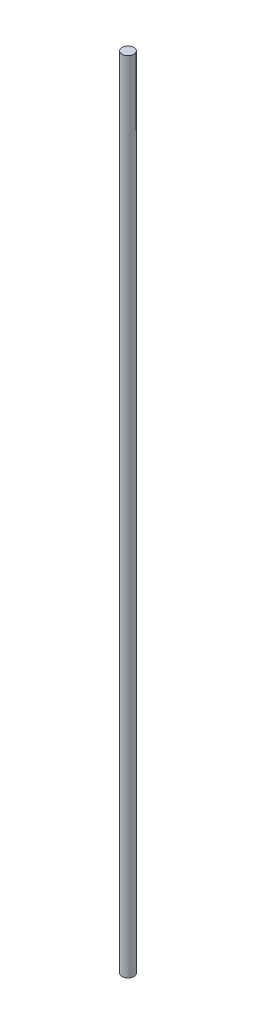
SolidWorks part; units mm, degrees
ref_plane "Спереди" through (0, 0, 0) normal (0, 0, 1) x (1, 0, 0)
ref_plane "Сверху" through (0, 0, 0) normal (0, 1, 0) x (1, 0, 0)
ref_plane "Справа" through (0, 0, 0) normal (1, 0, 0) x (0, 0, -1)
sketch "Эскиз2" plane through (0, 0, 0) normal (0, 0, 1) x (1, 0, 0)
  line L5 (-2.5, 167.95) -> (0, 167.95)
  line L6 (-2.5, 167.95) -> (-2.5, -167.95)
  line L7 (-2.5, -167.95) -> (0, -167.95)
  line L8 (0, 167.95) -> (0, -167.95)
  line L9 (-2.5, 167.95) -> (0, -167.95) construction
  line L10 (-2.5, -167.95) -> (0, 167.95) construction
  point P0 (-1.25, 0)
  point P5 (0, 0)
  dimension "D1" = 2.5
  dimension "D2" = 335.9
revolve "Повернуть1" add sketch "Эскиз2" angle 360 about L6
equation "\"Ширина груза\"= 160"
equation "\"Глубина груза\"= 240"
equation "\"Высота груза\"= 160"
equation "\"Ширина ячейки\"= \"Ширина груза\" + 10"
equation "\"Глубина ячейки\"= \"Глубина груза\" + 10"
equation "\"Высота ячейки\"= \"Высота груза\" + 10 + 13"
equation "\"Колво ячеек ширина\"= 2"
equation "\"Колво ячеек высота\"= 2"
equation "\"Толщина стенки\" = \"Толщина тонких панелей\""
equation "\"Крепление дверцы\"= 5 "
equation "\"Ширина рейки\"= \"Толщина шестерни\""
equation "\"Высота рейки\"= 20"
equation "\"Высота пола\" = 2*\"Толщина тонких панелей\""
equation "\"Колво полозьев\"= 5"
equation "\"Отступ рейки\"= 20"
equation "\"Глубина каретки\"= \"Глубина ячейки\" + 30 + \"Мотор Y высота корпуса\" + 20 + \"Удлинение платформы по глубине\""
equation "\"Длинна рейки\" = (\"Ширина ячейки\"+\"Толщина вертикальных стенок\"+\"Крепление дверцы\")*\"Колво ячеек ширина\"+\"Ширина ячейки выгрузки\"*\"Колво выгрузки\"+\"Толщина вертикальных стенок\"+2*\"Отступ крепления мотора фиксации\"-\"Крепление дверцы\"*\"Колво ячеек ширина\""
equation "\"Отступ шпильки\"= 26"
equation "\"Диаметр шпильки\"= 5"
equation "\"Длинна шпильки\" = (\"Высота ячейки\"+\"Толщина горизонтальных плит\"+\"Высота пола\")*\"Колво ячеек высота\"+2*(\"Толщина горизонтальных плит\"+\"Отступ рейки\")"
equation "\"D1@Эскиз2\"= \"Диаметр шпильки\" / 2"
equation "\"D2@Эскиз2\" = \"Глубина каретки\" - \"Мотор Y высота корпуса\" - \"Толщина стенки\""
equation "\"Ширина пластины\" = 50"
equation "\"Высота зона выгрузки\"= \"Высота ячейки\" * 2 + \"Толщина стенки\" * 2"
equation "\"Колво выгрузки\"= 1"
equation "\"Отступ крепления мотора фиксации\" = (70-\"Толщина вертикальных стенок\")/2"
equation "\"Мотор X ширина корпуса\"= 42.3"
equation "\"Мотор X высота корпуса\"= 42.3"
equation "\"Мотор X длина корпуса\"= 40"
equation "\"Мотор X вылет вала\"= 19.8"
equation "\"Мотор Y ширина корпуса\"= 42.3"
equation "\"Мотор Y высота корпуса\"= 42.3"
equation "\"Мотор Y длина корпуса\"= 48"
equation "\"Мотор Y вылет вала\"= 30"
equation "\"Мотор Z ширина корпуса\"= 42"
equation "\"Мотор Z высота корпуса\"= 42"
equation "\"Мотор Z длина корпуса\"= 40"
equation "\"Мотор Z вылет вала\"= 23"
equation "\"Мотор диаметр вала ПРЕДВ\"= 5"
equation "\"Мотор шаг крепления ПРЕДВ\"= 31"
equation "\"Мотор диаметр отверстий ПРЕДВ\"= 3"
equation "\"Мотор глубина отверстий ПРЕДВ\"= 4.5"
equation "\"Мотор диаметр буртика ПРЕДВ\"= 22"
equation "\"Мотор высота буртика ПРЕДВ\"= 2"
equation "\"Мотор диаметр шкива ПРЕДВ\"= 16"
equation "\"Мотор длина шкива ПРЕДВ\"= 12"
equation "\"Мотор отступ шкива ПРЕДВ\"= 5"
equation "\"Мотор X шаг градусов\"= 1.8"
equation "\"Мотор X ток А\"= 1.5"
equation "\"Мотор X сопротивление Ом\"= 1.3"
equation "\"Мотор X индуктивность мГн\"= 2"
equation "\"Мотор Y шаг градусов\"= 1.8"
equation "\"Мотор Y ток А\"= 2.2"
equation "\"Мотор Y сопротивление Ом\"= 0.9"
equation "\"Мотор Y индуктивность мГн\"= 2"
equation "\"Мотор Z шаг градусов\"= 1.8"
equation "\"Мотор Z ток А\"= 1"
equation "\"Мотор Z сопротивление Ом\"= 4"
equation "\"Мотор Z индуктивность мГн\"= 8"
equation "\"Мотор Y диаметр ротора\"= 25.78"
equation "\"Ширина ячейки выгрузки\" = \"Ширина ячейки\"+\"Толщина вертикальных стенок\"+2*\"Отступ крепления мотора фиксации\""
equation "\"Толщина тонких панелей\" = 6"
equation "\"Толщина вертикальных стенок\" = 6"
equation "\"Толщина горизонтальных плит\" = 6"
equation "\"Базовая высота корпуса\"= (\"Высота ячейки\"+\"Толщина тонких панелей\"+\"Высота пола\")*\"Колво ячеек высота\"+6*\"Толщина тонких панелей\"+\"Мотор X ширина корпуса\"+\"Мотор Y ширина корпуса\"+75"
equation "\"Высота корпуса\"= (\"Высота ячейки\"+\"Толщина горизонтальных плит\"+\"Высота пола\")*\"Колво ячеек высота\"+2*\"Толщина горизонтальных плит\"+4*\"Толщина тонких панелей\"+\"Мотор X ширина корпуса\"+\"Мотор Y ширина корпуса\"+75"
equation "\"Смещение центра корпуса\"= (\"Высота корпуса\"-\"Базовая высота корпуса\")/2-(\"Толщина горизонтальных плит\"-\"Толщина тонких панелей\")"
equation "\"Отметка пола\"= -\"Базовая высота корпуса\"/2+\"Толщина тонких панелей\""
equation "\"Отметка потолка\"= \"Отметка пола\"+\"Высота корпуса\"-2*\"Толщина горизонтальных плит\""
equation "\"Отметка верхней полки\"= \"Отметка потолка\"-(28+\"Толщина тонких панелей\")-\"Высота ячейки\"-\"Высота пола\""
equation "\"Отметка нижней полки\"= \"Отметка верхней полки\"-\"Высота ячейки\"-\"Высота пола\"-\"Толщина горизонтальных плит\""
equation "\"Толщина шестерни\"= 10"
equation "\"Переднее удлинение полозьев\"= 16.2"
equation "\"Зазор полозьев от задней стенки\"= 10"
equation "\"Удлинение платформы по глубине\"= \"Переднее удлинение полозьев\"+\"Зазор полозьев от задней стенки\"+15.7"
equation "\"Зазор между основанием и рейкой\"= 5"
